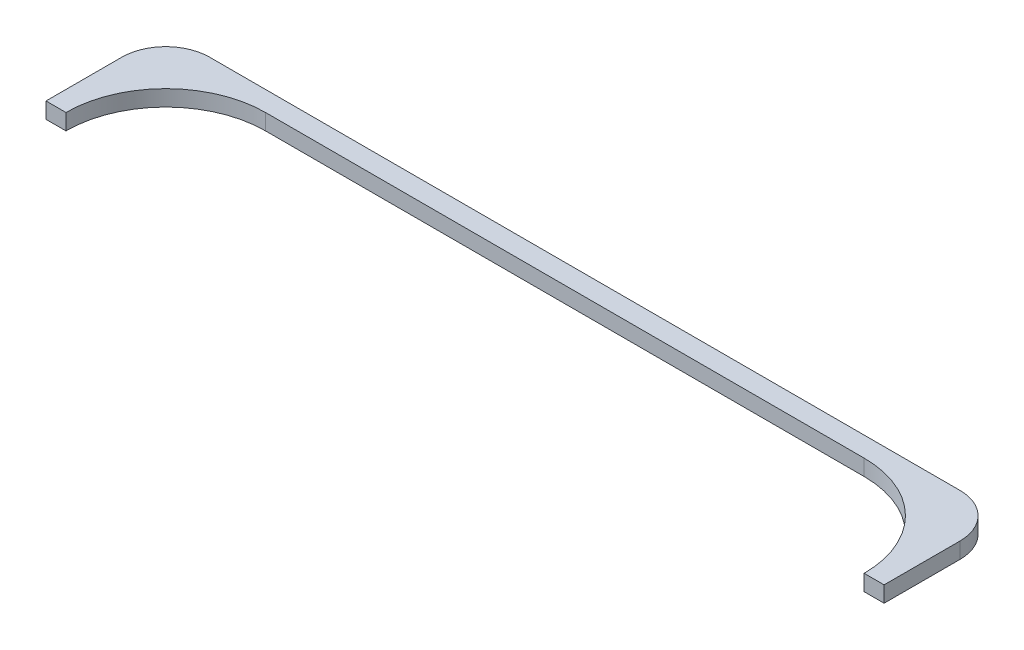
SolidWorks part; units mm, degrees
ref_plane "Front Plane" through (0, 0, 0) normal (0, 0, 1) x (1, 0, 0)
ref_plane "Top Plane" through (0, 0, 0) normal (0, 1, 0) x (1, 0, 0)
ref_plane "Right Plane" through (0, 0, 0) normal (1, 0, 0) x (0, 0, -1)
sketch "Sketch1" plane through (0, 0, 0) normal (0, 1, 0) x (1, 0, 0)
  line L1 (-133.35, -19.05) -> (133.35, -19.05)
  line L2 (-133.35, -19.05) -> (-133.35, 19.05)
  line L3 (-133.35, 19.05) -> (133.35, 19.05)
  line L4 (133.35, -19.05) -> (133.35, 19.05)
  line L5 (-133.35, -19.05) -> (133.35, 19.05) construction
  line L6 (-133.35, 19.05) -> (133.35, -19.05) construction
  point P0 (0, 0)
  dimension "D1" = 266.7
  dimension "D2" = 38.1
extrude "Bumper-Base" add sketch "Sketch1" along normal blind 5.08
sketch "Sketch2" plane through (0, 5.08, 0) normal (0, 1, 0) x (1, 0, 0)
  line L0 (-133.35, -19.05) -> (-127, -19.05) construction
  line L2 (-133.35, -19.05) -> (133.35, -19.05) construction
  line L7 (-127, -19.05) -> (-95.25, -19.05) construction
  line L9 (-95.25, 12.7) -> (0, 12.7)
  line L11 (-95.25, -19.05) -> (0, -19.05)
  line L12 (0, 12.7) -> (0, -19.05)
  arc A1 (-95.25, 12.7) -> (-127, -19.05) centre (-95.25, -19.05) ccw
  dimension "D1" = 6.35
  dimension "D2" = 31.75
extrude "Cut-Extrude1" cut sketch "Sketch2" against normal through all and the other way through all
ref_axis "Axis1" through (0, 5.08, 19.05) along (0, 0, -1)
ref_plane "Plane1" through (0, 0, 0) normal (1, 0, 0) x (0, 0, -1)
mirror "Mirror1" about plane through (0, 0, 0) normal (1, 0, 0) of "Cut-Extrude1"
fillet "Fillet1" radius 13.97 2 edges at (-133.35, 2.54, -19.05) (133.35, 2.54, -19.05)
equation "\"Foamcore\" = .1in"
equation "\"MDF\" = .2in"
equation "\"Gmaterial\"= \"MDF\""
equation "\"D1@Bumper-Base\" = \"Gmaterial\""
